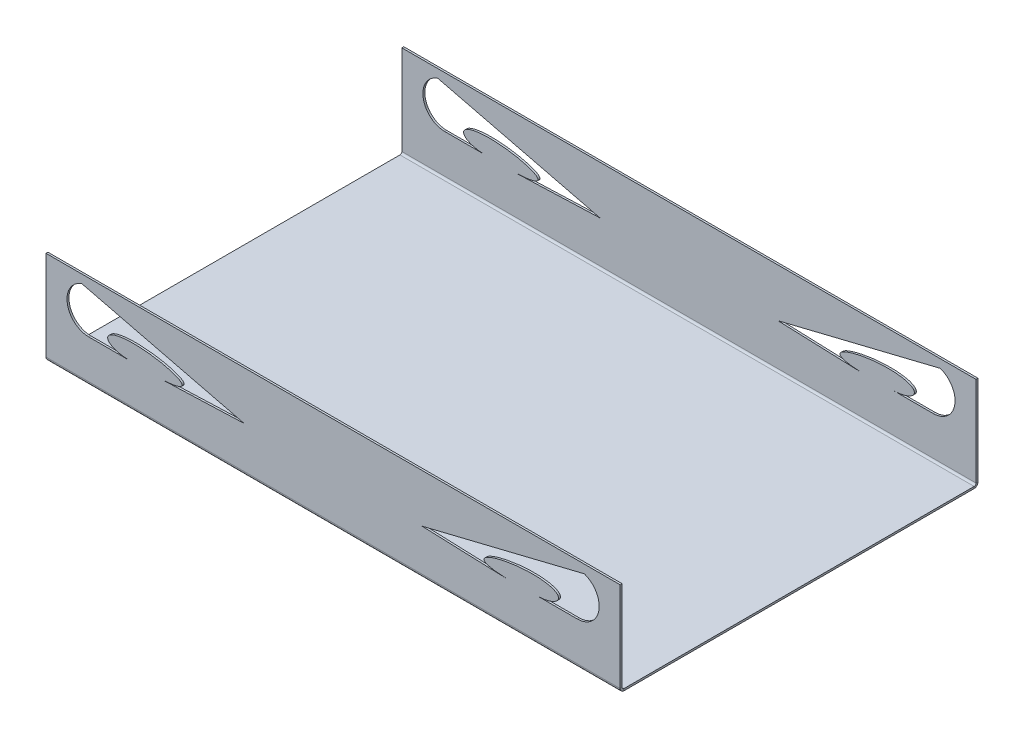
SolidWorks part; units mm, degrees
note: The reader was unsure of these and kept them because the rebuilt part matched: flange length of "Edge-Flange1".
ref_plane "Front Plane" through (0, 0, 0) normal (0, 0, 1) x (1, 0, 0)
ref_plane "Top Plane" through (0, 0, 0) normal (0, 1, 0) x (1, 0, 0)
ref_plane "Right Plane" through (0, 0, 0) normal (1, 0, 0) x (0, 0, -1)
sketch "Sketch1" plane through (0, 0, 0) normal (0, 1, 0) x (1, 0, 0)
  line L1 (-109.5, -67.5) -> (109.5, -67.5)
  line L2 (-109.5, -67.5) -> (-109.5, 67.5)
  line L3 (-109.5, 67.5) -> (109.5, 67.5)
  line L4 (109.5, -67.5) -> (109.5, 67.5)
  line L5 (-109.5, -67.5) -> (109.5, 67.5) construction
  line L6 (-109.5, 67.5) -> (109.5, -67.5) construction
  point P0 (0, 0)
  dimension "D1" = 135
  dimension "D2" = 219
base flange "Base-Flange1" sketch "Sketch1" thickness 0.7366 reverse thickness direction no parameters "D1"=0.7366
edge flange "Edge-Flange1" sketch "Sketch10" flange profiles "Sketch10", "Sketch11" flange angle 90 flange length 35.7366 flange position material outside bend radius 0.7366 thickness 0.7366 relief rectangular parameters "D6"=10, "D8"=1
sketch "Sketch10" plane through (0, 0, 67.5) normal (0, 0, 1) x (1, 0, 0)
  line L0 (-109.5, 0) -> (109.5, 0) construction
  line L1 (-109.5, 0) -> (109.5, 0)
  line L2 (-109.5, 0) -> (-109.5, 35)
  line L3 (-109.5, 35) -> (109.5, 35)
  line L4 (109.5, 35) -> (109.5, 0)
  dimension "D1" = 35
sketch "Sketch11" plane through (0, 0, -67.5) normal (0, 0, -1) x (-1, 0, 0)
  line L0 (-109.5, 0) -> (109.5, 0) construction
  line L1 (-109.5, 0) -> (109.5, 0)
  line L2 (-109.5, 0) -> (-109.5, 35)
  line L3 (-109.5, 35) -> (109.5, 35)
  line L4 (109.5, 35) -> (109.5, 0)
bend "EdgeBend1" bend radius 0.7366 bend angle 90 parameters "D5"=1
bend "EdgeBend2" bend radius 0.7366 bend angle 90 parameters "D5"=2
sketch "Sketch13" plane through (0, 0, 68.2366) normal (0, 0, 1) x (1, 0, 0)
  line L0 (77.8252, 15.538) -> (93.1292, 15.538)
  line L1 (95.8482, 31.7958) -> (33.9188, 16.5898)
  line L2 (33.9188, 16.5898) -> (66.2853, 15.3844)
  line L3 (66.2853, 15.3844) -> (33.9188, 16.5898) construction
  line L4 (33.9188, 16.5898) -> (95.8482, 31.7958) construction
  line L5 (95.8482, 31.7958) -> (93.1292, 15.538) construction
  line L6 (93.1292, 15.538) -> (77.8252, 15.538) construction
  line L7 (0, 0.7366) -> (0, 43.8961) construction
  line L8 (109.5, 0.7366) -> (-109.5, 0.7366) construction
  line L9 (-95.8482, 31.7958) -> (-33.9188, 16.5898)
  line L10 (-33.9188, 16.5898) -> (-66.2853, 15.3844)
  line L11 (-66.2853, 15.3844) -> (-33.9188, 16.5898) construction
  line L12 (-33.9188, 16.5898) -> (-95.8482, 31.7958) construction
  line L13 (-95.8482, 31.7958) -> (-93.1292, 15.538) construction
  line L14 (-93.1292, 15.538) -> (-77.8252, 15.538) construction
  line L15 (-77.8252, 15.538) -> (-93.1292, 15.538)
  arc A0 (93.1292, 15.538) -> (95.8482, 31.7958) centre (93.1292, 23.8943) ccw
  arc A1 (-93.1292, 15.538) -> (-95.8482, 31.7958) centre (-93.1292, 23.8943) cw
  spline S0 degree 4 poles (66.2853, 15.3844) (33.9188, 16.5898) (95.8482, 31.7958) (93.1292, 15.538) (77.8252, 15.538) knots 0 0 0 0 0 1 1 1 1 1
  spline S1 degree 4 poles (-66.2853, 15.3844) (-33.9188, 16.5898) (-95.8482, 31.7958) (-93.1292, 15.538) (-77.8252, 15.538) knots 0 0 0 0 0 1 1 1 1 1
extrude "Cut-Extrude1" cut sketch "Sketch13" against normal through all normal cut yes
sketch "Bend-Lines1" plane through (0, 0, 0) normal (0, 1, 0) x (1, 0, 0)
sketch "Bounding-Box1" plane through (0, 0, 0) normal (0, 1, 0) x (1, 0, 0)
sheet metal parameters "Sheet-Metal1" thickness 0.7366 parameters "D1"=0.7366
flat pattern "Flat-Pattern1" [suppressed]
sketch "Bend-Lines2" plane through (0, 0, 0) normal (0, 1, 0) x (1, 0, 0)
sketch "Bounding-Box2" [suppressed] plane through (0, 0, 0) normal (0, 1, 0) x (1, 0, 0)
sheet metal parameters "Sheet-Metal2" thickness 0.7366 parameters "D1"=0.7366
flat pattern "Flat-Pattern1" [suppressed]
sketch "Bend-Lines2" plane through (0, 0, 0) normal (0, 1, 0) x (1, 0, 0)
sketch "Bounding-Box2" [suppressed] plane through (0, 0, 0) normal (0, 1, 0) x (1, 0, 0)
bend of the flat pattern "Flatten-<EdgeBend1>1"
bend of the flat pattern "Flatten-<EdgeBend2>1"
sheet metal parameters "Sheet-Metal3" thickness 0.7366 parameters "D1"=0.7366
flat pattern "Flat-Pattern1" [suppressed]
sketch "Bend-Lines2" plane through (0, 0, 0) normal (0, 1, 0) x (1, 0, 0)
sketch "Bounding-Box2" [suppressed] plane through (0, 0, 0) normal (0, 1, 0) x (1, 0, 0)
bend of the flat pattern "Flatten-<EdgeBend1>1"
bend of the flat pattern "Flatten-<EdgeBend2>1"
